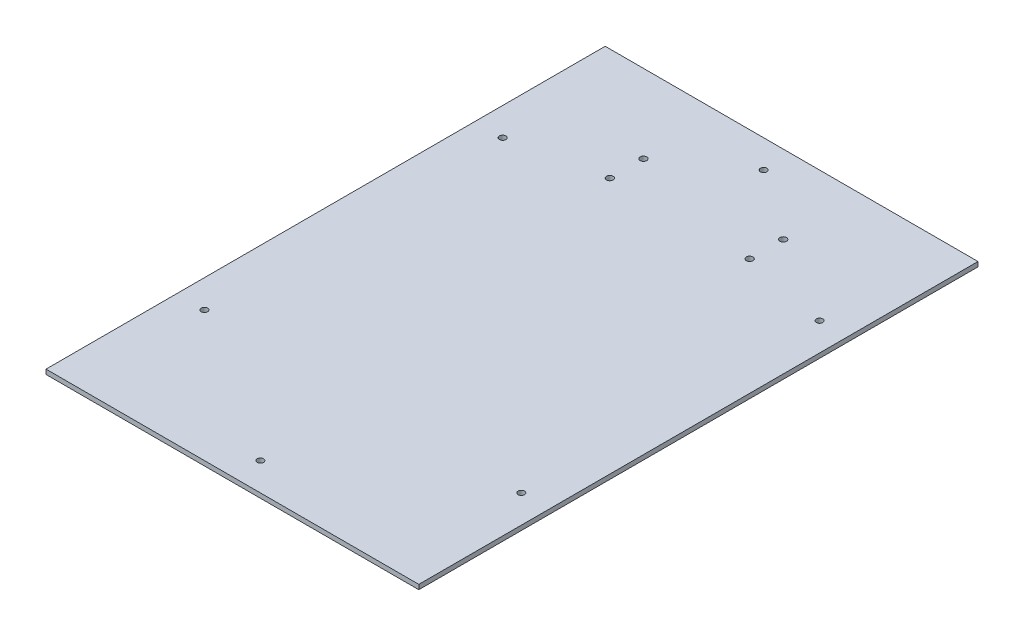
SolidWorks part; units mm, degrees
material "PC High Viscosity"
ref_plane "Front Plane" through (0, 0, 0) normal (0, 0, 1) x (1, 0, 0)
ref_plane "Top Plane" through (0, 0, 0) normal (0, 1, 0) x (1, 0, 0)
ref_plane "Right Plane" through (0, 0, 0) normal (1, 0, 0) x (0, 0, -1)
sketch "Sketch1" plane through (0, 0, 0) normal (0, 1, 0) x (1, 0, 0)
  line L1 (-148.9254, 230.8343) -> (105.0746, 230.8343)
  line L2 (-148.9254, 230.8343) -> (-148.9254, -150.1657)
  line L3 (-148.9254, -150.1657) -> (105.0746, -150.1657)
  line L4 (105.0746, 230.8343) -> (105.0746, -150.1657)
  point P0 (0, 0)
  dimension "D1" = 254
  dimension "D2" = 381
extrude "Boss-Extrude1" add sketch "Sketch1" along normal blind 3.175
sketch "Sketch18" plane through (0, 0, 0) normal (0, -1, 0) x (1, 0, 0)
  line L0 (-148.9254, -230.8343) -> (-148.9254, 150.1657) construction
  line L2 (-148.9254, 150.1657) -> (105.0746, 150.1657) construction
  point P0 (-69.5504, -154.6343)
  point P1 (25.6996, -154.6343)
  point P2 (25.6996, -177.4943)
  point P3 (-69.5504, -177.4943)
  dimension "D1" = 22.86
  dimension "D2" = 22.86
  dimension "D3" = 95.25
  dimension "D4" = 95.25
  dimension "D5" = 79.375
  dimension "D6" = 304.8
hole_wizard "#16 (0.177) Diameter Hole1" positions "Sketch19" profile "Sketch21" hole size "#16" standard "ANSI Inch" end condition through all
sketch "Sketch19" plane through (0, 0, 0) normal (0, -1, 0) x (-1, 0, 0)
  point P0 (-25.6996, 177.4943)
  point P3 (-25.6996, 154.6343)
  point P6 (69.5504, 154.6343)
  point P9 (69.5504, 177.4943)
sketch "Sketch21" plane through (25.6996, 0, -177.4943) normal (1, 0, 0) x (0, 0, -1)
  line L0 (0, 0) -> (0, 3.175)
  line L1 (0, 3.175) -> (2.2479, 3.175)
  line L2 (2.2479, 3.175) -> (2.2479, 0)
  line L5 (2.2479, 0) -> (0, 0)
  line L11 (0, -6.35) -> (0, 107.95) construction
  dimension "Thru Hole Dia." = 4.4958
  dimension "Thru Hole Depth" = 3.175
sketch "Sketch22" plane through (0, 0, 0) normal (0, -1, 0) x (1, 0, 0)
  line L0 (105.0746, -230.8343) -> (105.0746, 150.1657) construction
  line L1 (-148.9254, -230.8343) -> (-148.9254, 150.1657) construction
  line L2 (-148.9254, 150.1657) -> (105.0746, 150.1657) construction
  line L3 (-148.9254, -230.8343) -> (105.0746, -230.8343) construction
  point P0 (86.0246, 61.2657)
  point P1 (86.0246, -141.9343)
  point P2 (-129.8754, -141.9343)
  point P3 (-129.8754, 61.2657)
  point P4 (-21.9254, 131.1157)
  point P16 (-21.9254, -211.7843)
  dimension "D1" = 19.05
  dimension "D2" = 19.05
  dimension "D3" = 88.9
  dimension "D4" = 88.9
  dimension "D5" = 19.05
  dimension "D6" = 19.05
  dimension "D7" = 127
hole_wizard "11/64 (0.17188) Diameter Hole1" positions "Sketch23" profile "Sketch24" hole size "11/64" standard "ANSI Inch" end condition through all
sketch "Sketch23" plane through (0, 0, 0) normal (0, -1, 0) x (-1, 0, 0)
  point P0 (-86.0246, 141.9343)
  point P3 (21.9254, 211.7843)
  point P6 (129.8754, 141.9343)
  point P9 (129.8754, -61.2657)
  point P12 (21.9254, -131.1157)
  point P15 (-86.0246, -61.2657)
sketch "Sketch24" plane through (86.0246, 0, -141.9343) normal (1, 0, 0) x (0, 0, -1)
  line L0 (0, 0) -> (0, 3.175)
  line L1 (0, 3.175) -> (2.1829, 3.175)
  line L2 (2.1829, 3.175) -> (2.1829, 0)
  line L5 (2.1829, 0) -> (0, 0)
  line L11 (0, -6.35) -> (0, 107.95) construction
  dimension "Thru Hole Dia." = 4.3658
  dimension "Thru Hole Depth" = 3.175
